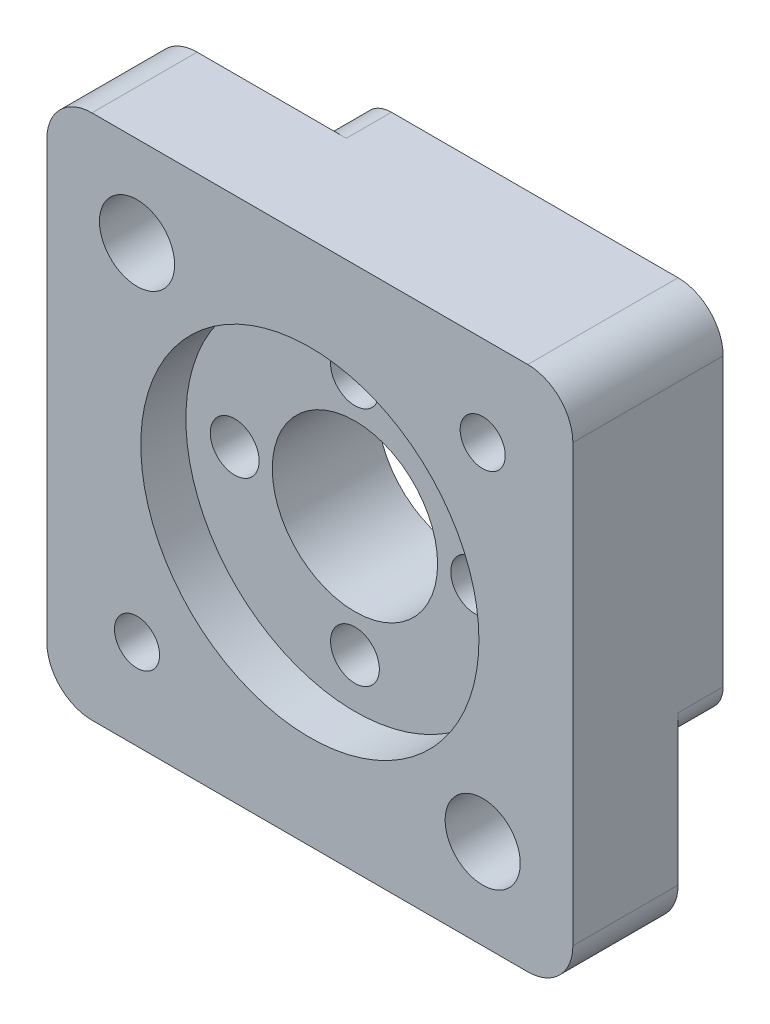
SolidWorks part; units mm, degrees
ref_plane "Front Plane" through (0, 0, 0) normal (0, 0, 1) x (1, 0, 0)
ref_plane "Top Plane" through (0, 0, 0) normal (0, 1, 0) x (1, 0, 0)
ref_plane "Right Plane" through (0, 0, 0) normal (1, 0, 0) x (0, 0, -1)
sketch "Sketch1" plane through (0, 0, 0) normal (0, 0, 1) x (1, 0, 0)
  line L1 (-17.5, -17.5) -> (17.5, -17.5)
  line L2 (-17.5, -17.5) -> (-17.5, 17.5)
  line L3 (-17.5, 17.5) -> (17.5, 17.5)
  line L4 (17.5, -17.5) -> (17.5, 17.5)
  line L5 (-17.5, -17.5) -> (17.5, 17.5) construction
  line L6 (-17.5, 17.5) -> (17.5, -17.5) construction
  line L7 (-11.5, -11.5) -> (11.5, -11.5) construction
  line L8 (-11.5, -11.5) -> (-11.5, 11.5) construction
  line L9 (-11.5, 11.5) -> (11.5, 11.5) construction
  line L10 (11.5, -11.5) -> (11.5, 11.5) construction
  line L11 (-11.5, -11.5) -> (11.5, 11.5) construction
  line L12 (-11.5, 11.5) -> (11.5, -11.5) construction
  circle A0 centre (0, 0) radius 5.5
  circle A1 centre (-11.5, 11.5) radius 2.5
  circle A2 centre (11.5, 11.5) radius 1.5
  circle A3 centre (11.5, -11.5) radius 2.5
  circle A4 centre (-11.5, -11.5) radius 1.5
  circle A5 centre (0, 0) radius 11 construction
  point P0 (0, 0)
  point P10 (11.5, 11.5)
  point P19 (0, 0)
  dimension "D1" = 11
  dimension "D4" = 5
  dimension "D6" = 22
  dimension "D5" = 3
  dimension "D2" = 35
  dimension "D3" = 6
extrude "Boss-Extrude1" add sketch "Sketch1" along normal blind 10
fillet "Fillet1" radius 3 4 edges at (17.5, -17.5, 5) (17.5, 17.5, 5) (-17.5, -17.5, 5) (-17.5, 17.5, 5)
sketch "Sketch2" plane through (0, 0, 10) normal (0, 0, 1) x (1, 0, 0)
  circle A0 centre (0, 0) radius 8 construction
  circle A1 centre (-8, 0) radius 1.625
  circle A2 centre (0, 8) radius 1.625
  circle A3 centre (8, 0) radius 1.625
  circle A4 centre (0, -8) radius 1.625
  point P14 (0, 0)
  dimension "D1" = 16
  dimension "D2" = 3.25
  dimension "D3" = 4
extrude "Cut-Extrude1" cut sketch "Sketch2" against normal blind 10
sketch "Sketch3" plane through (0, 0, 10) normal (0, 0, 1) x (1, 0, 0)
  circle A0 centre (0, 0) radius 11.25
  dimension "D1" = 22.5
extrude "Cut-Extrude2" cut sketch "Sketch3" against normal blind 3
sketch "Sketch5" plane through (0, 0, 0) normal (0, 0, -1) x (-1, 0, 0)
  line L0 (-14.5, 17.5) -> (14.5, 17.5) construction
  line L1 (7.2574, 15.7426) -> (15.8447, 24.33)
  line L2 (15.8447, 24.33) -> (24.33, 15.8447)
  line L3 (24.33, 15.8447) -> (15.7426, 7.2574)
  line L4 (0, 0) -> (20.0874, 20.0874) construction
  line L5 (0, 0) -> (11.5, -11.5) construction
  line L6 (-24.33, -15.8447) -> (-15.8447, -24.33)
  line L7 (-15.8447, -24.33) -> (-7.2574, -15.7426)
  line L8 (-15.7426, -7.2574) -> (-24.33, -15.8447)
  arc A0 (-7.2574, -15.7426) -> (-15.7426, -7.2574) centre (-11.5, -11.5) ccw
  arc A1 (7.2574, 15.7426) -> (15.7426, 7.2574) centre (11.5, 11.5) ccw
  arc A2 (-15.7426, -7.2574) -> (-7.2574, -15.7426) centre (-11.5, -11.5) cw
  circle M12 centre (-11.5, -11.5) radius 2.5
  circle M13 centre (11.5, 11.5) radius 2.5
  line M14 (-17.5, 14.5) -> (-17.5, -14.5)
  arc M15 (-17.5, -14.5) -> (-14.5, -17.5) centre (-14.5, -14.5) ccw
  line M16 (-14.5, -17.5) -> (14.5, -17.5)
  line M18 (17.5, -14.5) -> (17.5, 14.5)
  arc M19 (17.5, 14.5) -> (14.5, 17.5) centre (14.5, 14.5) ccw
  line M20 (14.5, 17.5) -> (-14.5, 17.5)
extrude "Cut-Extrude4" cut sketch "Sketch5" against normal blind 3 contours L7 A0 L8 M14 M15 M16 M12 | L1 A1 L3 M18 M19 M20 M13 region at (-8.256, 16.5013, 0) region at (16.5013, -8.256, 0)
fillet "Fillet2" radius 2 4 edges at (-9.0147, 17.5, 1.5) (-17.5, 9.0147, 1.5) (9.0147, -17.5, 1.5) (17.5, -9.0147, 1.5)
